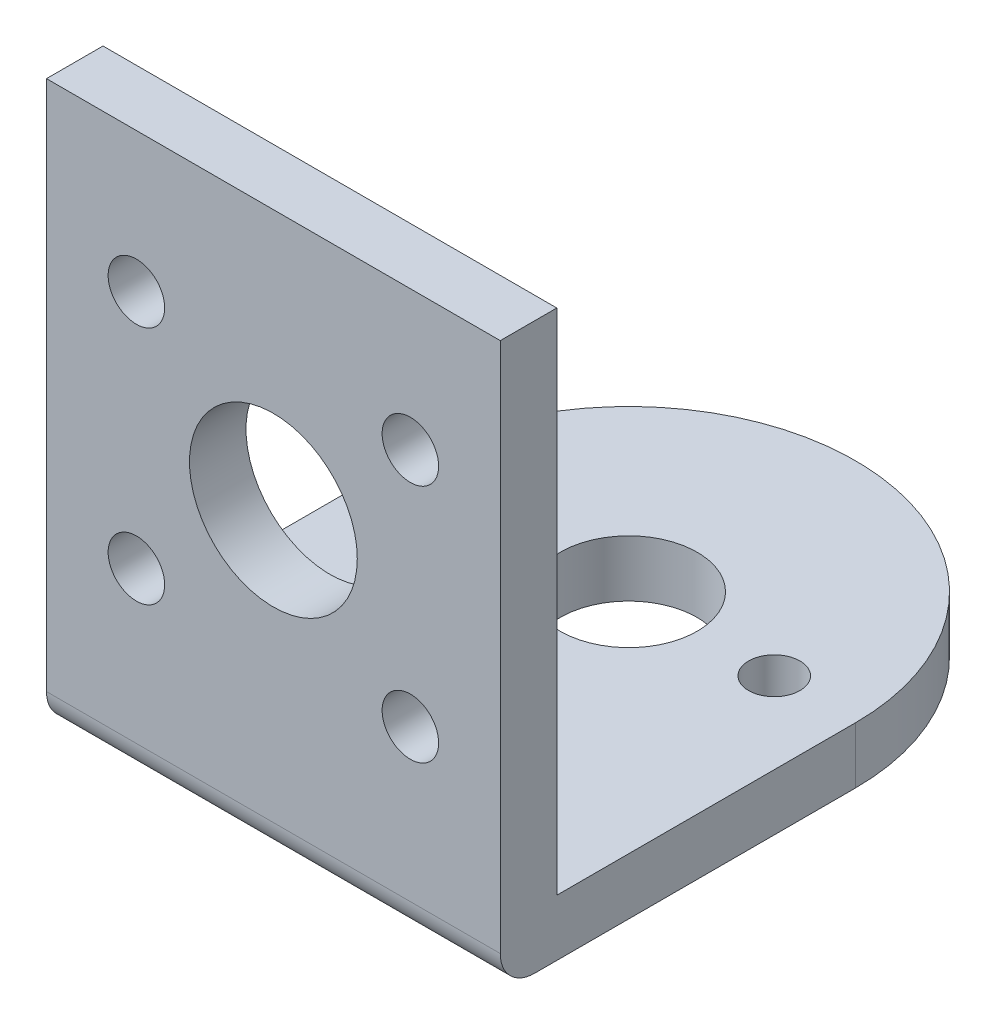
SolidWorks part; units mm, degrees
ref_plane "Front Plane" through (0, 0, 0) normal (0, 0, 1) x (1, 0, 0)
ref_plane "Top Plane" through (0, 0, 0) normal (0, 1, 0) x (1, 0, 0)
ref_plane "Right Plane" through (0, 0, 0) normal (1, 0, 0) x (0, 0, -1)
other "Configuration Table"
sketch "Base Face" plane through (0, 0, 0) normal (0, 1, 0) x (1, 0, 0)
  line L2 (-13.25, 0) -> (-13.25, -20.75)
  line L3 (-13.25, -20.75) -> (13.25, -20.75)
  line L4 (13.25, 0) -> (13.25, -20.75)
  line L5 (-13.25, -20.75) -> (13.25, -20.75)
  line L6 (-13.25, -20.75) -> (-13.25, -17.45)
  line L7 (-13.25, -17.45) -> (13.25, -17.45)
  line L8 (13.25, -20.75) -> (13.25, -17.45)
  arc A0 (13.25, 0) -> (-13.25, 0) centre (0, 0) ccw
  circle A1 centre (0, 0) radius 4
  circle A2 centre (-8.5, 0) radius 1.5
  circle A3 centre (8.5, 0) radius 1.5
  dimension "D1" = 26.5
  dimension "D2" = 8
  dimension "D3" = 3
  dimension "D4" = 3
  dimension "D6" = 13.25
  dimension "D5" = 20.75
extrude "Base" add sketch "Base Face" along normal blind 3.3 contours A2 | A1 | A3 | L3 L4 A0 L2
sketch "Top sketch" plane through (0, 0, 20.75) normal (0, 0, 1) x (1, 0, 0)
  line L1 (-13.25, 0) -> (13.25, 0)
  line L2 (-13.25, 0) -> (-13.25, 33)
  line L3 (-13.25, 33) -> (13.25, 33)
  line L4 (13.25, 0) -> (13.25, 33)
  circle A5 centre (0, 17.8) radius 4.9
  circle A6 centre (8, 10.85) radius 1.65
  circle A7 centre (8, 24.85) radius 1.65
  circle A8 centre (-8, 10.85) radius 1.65
  circle A9 centre (-8, 24.85) radius 1.65
  point P15 (-7.8674, 24.85)
  point P16 (-7.8121, 24.85)
  point P20 (-7.8242, 10.85)
  point P22 (0, 0)
  dimension "D1" = 15.2
  dimension "D3" = 14
  dimension "D2" = 8.15
  dimension "D4" = 3.3
  dimension "D7" = 9.8
  dimension "D5" = 16
  dimension "D6" = 26.5
  dimension "D8" = 13.25
sketch "Sketch3" plane through (0, 0, 20.75) normal (0, 0, 1) x (1, 0, 0)
  line L0 (-13.25, 0) -> (13.25, 0)
  line L1 (-13.25, 0) -> (-13.25, 33)
  line L2 (-13.25, 33) -> (13.25, 33)
  line L3 (13.25, 0) -> (13.25, 33)
  circle A0 centre (0, 17.8) radius 4.9
  circle A1 centre (8, 10.85) radius 1.65
  circle A2 centre (8, 24.85) radius 1.65
  circle A3 centre (-8, 10.85) radius 1.65
  circle A4 centre (-8, 24.85) radius 1.65
  dimension "D1" = 14
extrude "Boss-Extrude2" add sketch "Sketch3" against normal blind 3.3
fillet "Fillet1" radius 2 1 edges at (0, 0, 20.75)
